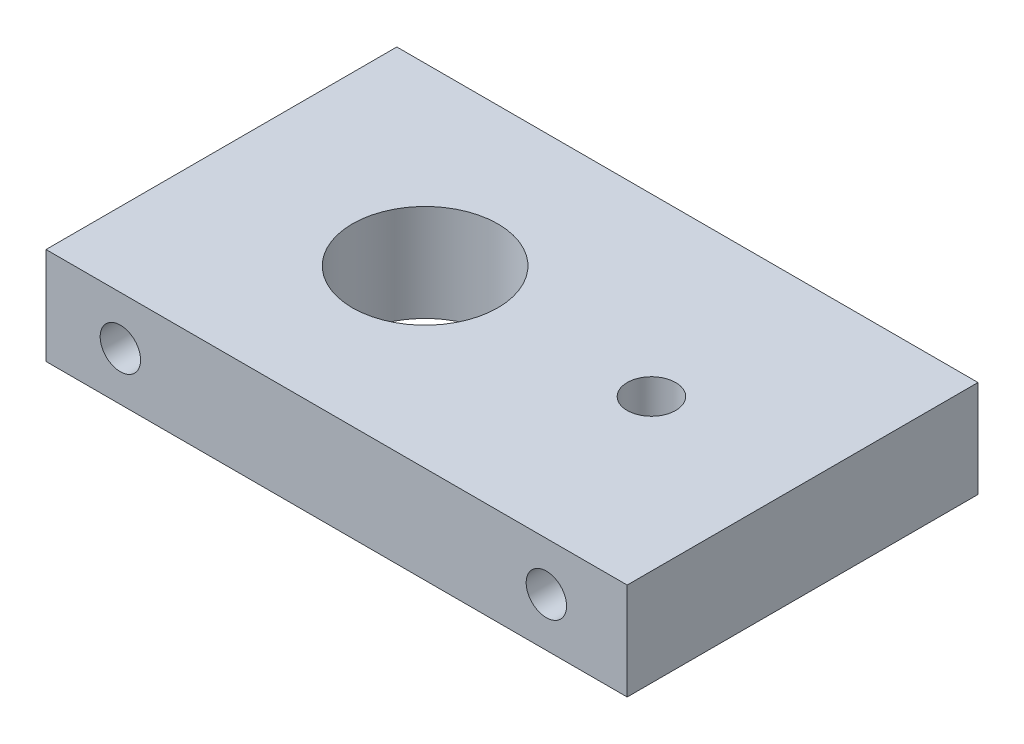
SolidWorks part; units mm, degrees
ref_plane "Ebene vorne" through (0, 0, 0) normal (0, 0, 1) x (1, 0, 0)
ref_plane "Ebene oben" through (0, 0, 0) normal (0, 1, 0) x (1, 0, 0)
ref_plane "Ebene rechts" through (0, 0, 0) normal (1, 0, 0) x (0, 0, -1)
sketch "Skizze1" plane through (0, 0, 0) normal (0, 0, 1) x (1, 0, 0)
  line L1 (-23.35, 231) -> (23.35, 231)
  line L2 (-23.35, 231) -> (-23.35, 237)
  line L3 (-23.35, 237) -> (23.35, 237)
  line L4 (23.35, 231) -> (23.35, 237)
  line L5 (-23.35, 231) -> (23.35, 237) construction
  line L6 (-23.35, 237) -> (23.35, 231) construction
  point P0 (0, 234)
sketch "Skizze2" plane through (0, 0, 0) normal (0, 1, 0) x (1, 0, 0)
  line L1 (-12.6, 12.65) -> (25.15, 12.65)
  line L2 (25.15, 12.65) -> (25.15, -12.65)
  line L3 (25.15, -12.65) -> (-12.6, -12.65)
  line L5 (-12.6, 10.85) -> (23.35, 10.85)
  line L6 (23.35, 10.85) -> (23.35, -10.85)
  line L7 (23.35, -10.85) -> (-12.6, -10.85)
  arc A0 (-12.6, 12.65) -> (-12.6, -12.65) centre (-12.6, 0) ccw
  arc A1 (-12.6, 10.85) -> (-12.6, -10.85) centre (-12.6, 0) ccw
sketch "Skizze3" plane through (0, 0, 0) normal (0, 0, 1) x (1, 0, 0)
  line L1 (-23.35, 231) -> (23.35, 231)
  line L2 (-23.35, 231) -> (-23.35, 237)
  line L3 (-23.35, 237) -> (23.35, 237)
  line L4 (23.35, 231) -> (23.35, 237)
  line L5 (-23.35, 231) -> (23.35, 237) construction
  line L6 (-23.35, 237) -> (23.35, 231) construction
  point P0 (0, 234)
extrude "Aufsatz-Linear austragen1" add sketch "Skizze3" along normal up to vertex (12.65 mm away) and the other way up to vertex (12.65 mm away) up to point (25.15, 0, 12.65) other way up to point (25.15, 0, -12.65)
sketch "Skizze4" plane through (0, 0, 0) normal (0, 1, 0) x (1, 0, 0)
  line L0 (23.35, -10.85) -> (23.35, 10.85)
  line L1 (23.35, 10.85) -> (23.35, -10.85) construction
  line L2 (23.35, 10.85) -> (-12.6, 10.85)
  line L3 (-76.8863, 0) -> (76.8863, 0) construction
  line L4 (23.35, -10.85) -> (-12.6, -10.85)
  line L5 (-12.6, 10.85) -> (-12.6, -10.85)
  point P15 (23.35, 0)
extrude "Schnitt-Linear austragen1" cut sketch "Skizze4" along normal up to surface (237 mm away) flip side to cut up to face at (0, 237, 0)
sketch "HoleLeadscrewLinearGuide" plane through (0, 0, 0) normal (0, 1, 0) x (1, 0, 0)
  circle A0 centre (14, 0) radius 1.5
  circle A1 centre (0, 0) radius 4.5
sketch "Skizze7" plane through (0, 0, 0) normal (0, 1, 0) x (1, 0, 0)
  circle A0 centre (0, 0) radius 4.5
  circle A1 centre (14, 0) radius 1.5
extrude "Schnitt-Linear austragen2" cut sketch "Skizze7" along normal up to surface (237 mm away) up to face at (5.375, 237, 0)
sketch "ThreadHolesSide" plane through (0, 0, 0) normal (0, 0, 1) x (1, 0, 0)
  line L0 (0, 234) -> (28.7572, 234) construction
  line L3 (0, 530.8289) -> (28.7572, 530.8289) construction
  circle A0 centre (18.35, 234) radius 1.25
  circle A1 centre (-8, 234) radius 1.25
  circle A2 centre (19.35, 530.8289) radius 1.25
  circle A3 centre (-8, 530.8289) radius 1.25
  point P18 (0, 0)
extrude "Schnitt-Linear austragen3" cut sketch "ThreadHolesSide" along normal blind 6 from surface starting at face at (5.375, 234, -10.85)
extrude "Schnitt-Linear austragen4" cut sketch "ThreadHolesSide<2>" against normal blind 6 from surface starting at face at (5.375, 234, 10.85)
sketch "ThreadHolesSide<2>" plane through (0, 0, 0) normal (0, 0, 1) x (1, 0, 0) same geometry as "ThreadHolesSide"
